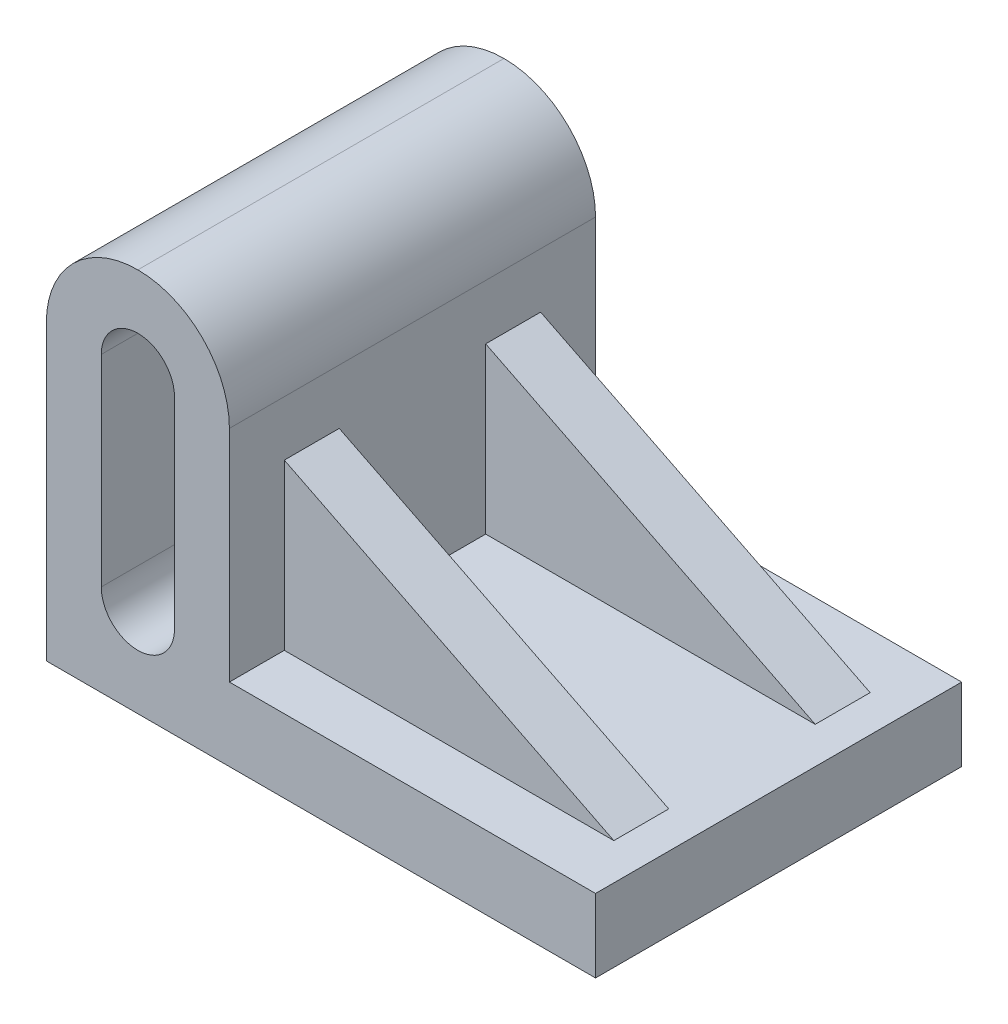
SolidWorks part; units mm, degrees
ref_plane "Front Plane" through (0, 0, 0) normal (0, 0, 1) x (1, 0, 0)
ref_plane "Top Plane" through (0, 0, 0) normal (0, 1, 0) x (1, 0, 0)
ref_plane "Right Plane" through (0, 0, 0) normal (1, 0, 0) x (0, 0, -1)
sketch "Sketch1" plane through (0, 0, 0) normal (0, 0, 1) x (1, 0, 0)
  line L0 (0, 0) -> (0, 105)
  line L1 (0, 105) -> (50, 105)
  line L2 (50, 105) -> (50, 20)
  line L3 (50, 20) -> (150, 20)
  line L4 (150, 20) -> (150, 0)
  line L5 (150, 0) -> (0, 0)
  dimension "D1" = 150
  dimension "D2" = 20
  dimension "D3" = 105
  dimension "D4" = 50
extrude "Boss-Extrude1" add sketch "Sketch1" along normal blind 50 and the other way blind 50
fillet "Fillet5" radius 25 1 edges at (0, 105, 0)
fillet "Fillet4" radius 25 1 edges at (50, 105, 0)
sketch "Sketch3" plane through (0, 0, 50) normal (0, 0, 1) x (1, 0, 0)
  line L0 (25, 80) -> (25, 25) construction
  line L1 (35, 80) -> (35, 25)
  line L2 (15, 80) -> (15, 25)
  line L3 (0, 0) -> (150, 0) construction
  line L4 (50, 20) -> (50, 80) construction
  arc A0 (35, 80) -> (15, 80) centre (25, 80) ccw
  arc A1 (15, 25) -> (35, 25) centre (25, 25) ccw
  point P2 (25, 52.5)
  dimension "D3" = 10
  dimension "D1" = 55
  dimension "D2" = 25
  dimension "D4" = 25
extrude "Cut-Extrude1" cut sketch "Sketch3" against normal through all
sketch "Sketch5" plane through (0, 0, 0) normal (0, 0, 1) x (1, 0, 0)
  line L0 (50, 65) -> (140, 20)
  line L1 (50, 20) -> (50, 80) construction
  line L2 (150, 20) -> (50, 20) construction
  line L3 (140, 20) -> (50, 20)
  line L4 (50, 20) -> (50, 65)
  line L5 (150, 0) -> (150, 20) construction
  dimension "D1" = 10
  dimension "D2" = 45
extrude "Boss-Extrude2" add sketch "Sketch5" along normal blind 15 from offset 20
sketch "Sketch9" plane through (0, 0, 20) normal (0, 0, -1) x (-1, 0, 0)
  line L0 (-50, 20) -> (-50, 65)
  line L1 (-50, 20) -> (-50, 80) construction
  line L2 (-50, 65) -> (-50, 20) construction
  line L3 (-50, 65) -> (-140, 20)
  line L4 (-150, 20) -> (-50, 20) construction
  line L5 (-140, 20) -> (-50, 65) construction
  line L6 (-140, 20) -> (-50, 20)
  dimension "D1" = 45
extrude "Boss-Extrude3" add sketch "Sketch9" along normal blind 15 from offset 40
